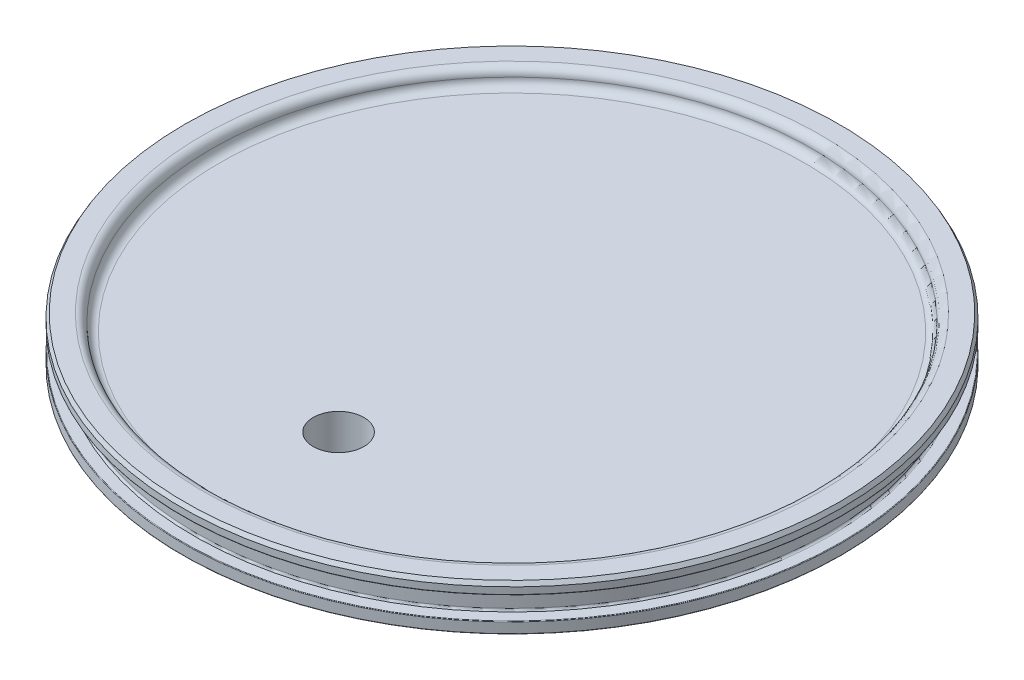
SolidWorks part; units mm, degrees
material "6061-T6 (SS)"
ref_plane "Front Plane" through (0, 0, 0) normal (0, 0, 1) x (1, 0, 0)
ref_plane "Top Plane" through (0, 0, 0) normal (0, 1, 0) x (1, 0, 0)
ref_plane "Right Plane" through (0, 0, 0) normal (1, 0, 0) x (0, 0, -1)
sketch "Sketch1" plane through (0, 0, 0) normal (0, 0, 1) x (1, 0, 0)
  line L0 (0, 48.1922) -> (0, -25.6743) construction
  line L1 (0, 0) -> (72.39, 0)
  line L2 (72.39, 0) -> (72.39, 2.4638)
  line L3 (72.39, 2.4638) -> (69.469, 2.4638)
  line L4 (69.469, 2.4638) -> (69.469, 7.4422)
  line L5 (69.469, 7.4422) -> (72.39, 7.4422)
  line L6 (72.39, 7.4422) -> (72.39, 9.906)
  line L7 (72.39, 9.906) -> (66.04, 9.906)
  line L8 (66.04, 9.906) -> (66.04, 6.35)
  line L9 (66.04, 6.35) -> (0, 6.35)
  line L10 (0, 6.35) -> (0, 0)
  dimension "D1" = 144.78
  dimension "D2" = 4.9784
  dimension "D3" = 2.921
  dimension "D5" = 6.35
  dimension "D6" = 6.35
  dimension "D4" = 9.906
revolve "Revolve1" add sketch "Sketch1" angle 360 about L0
sketch "Sketch6" plane through (0, 0, 0) normal (0, -1, 0) x (1, 0, 0)
  circle A0 centre (0, 0) radius 66.04
  dimension "D1" = 132.08
extrude "Boss-Extrude1" add sketch "Sketch6" along normal blind 2.54
fillet "CNC ID Fillet" radius 0.4064 3 edges at (-69.469, 7.4422, 0) (-69.469, 2.4638, 0) (66.04, 0, 0)
fillet "CNC OD Fillet" radius 0.127 4 edges at (-72.39, 7.4422, 0) (-72.39, 2.4638, 0) (66.04, -2.54, 0) (-72.39, 0, 0)
chamfer "CNC Chamfers" distance 0.508 angle 60 1 edges at (-72.39, 9.906, 0) first distance on face at (-66.04, 9.906, 0)
fillet "CNC Bore Fillet" radius 1.778 2 edges at (-66.04, 6.35, 0) (-66.04, 9.906, 0)
hole_wizard "Pipe Tap Drill for 1/4 Tap - To Injector" positions "Sketch15" profile "Sketch16" hole size "1/4" standard "ANSI Inch" end condition through all
sketch "Sketch15" plane through (0, -2.54, 0) normal (0, -1, 0) x (-1, 0, 0)
  point P4 (0, -38.1)
  dimension "D1" = 38.1
sketch "Sketch16" plane through (0, -2.54, 38.1) normal (1, 0, 0) x (0, 0, -1)
  line L0 (0, 0) -> (0, 12.446)
  line L1 (0, 12.446) -> (5.5626, 12.446)
  line L2 (5.5626, 12.446) -> (5.5626, 0)
  line L5 (5.5626, 0) -> (0, 0)
  line L11 (0, -6.35) -> (0, 107.95) construction
  dimension "Thru Hole Dia." = 11.1252
  dimension "Thru Hole Depth" = 12.446
equation "\"D3@Sketch1\"=(5.7-5.47)/2"
